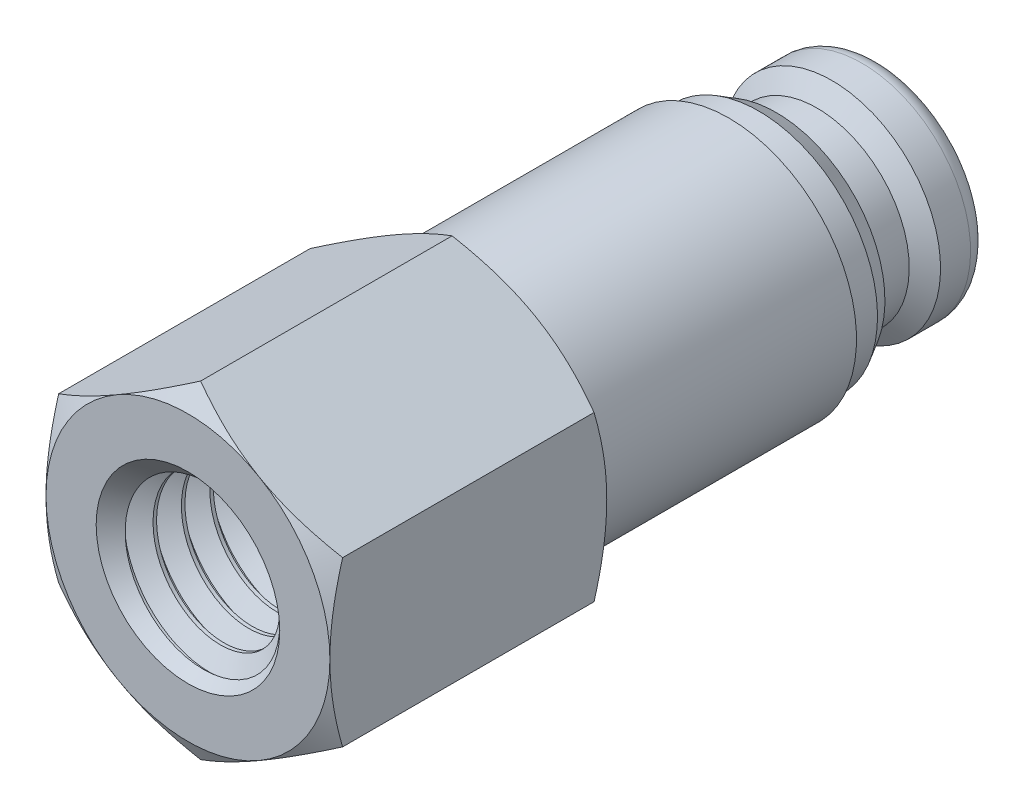
SolidWorks part; units mm, degrees
ref_plane "Front Plane" through (0, 0, 0) normal (0, 0, 1) x (1, 0, 0)
ref_plane "Top Plane" through (0, 0, 0) normal (0, 1, 0) x (1, 0, 0)
ref_plane "Right Plane" through (0, 0, 0) normal (1, 0, 0) x (0, 0, -1)
sketch "Sketch1" plane through (0, 0, 0) normal (0, 0, 1) x (1, 0, 0)
  line L1 (0, 4.6188) -> (-4, 2.3094)
  line L2 (-4, 2.3094) -> (-4, -2.3094)
  line L3 (-4, -2.3094) -> (0, -4.6188)
  line L4 (0, -4.6188) -> (4, -2.3094)
  line L5 (4, -2.3094) -> (4, 2.3094)
  line L6 (4, 2.3094) -> (0, 4.6188)
  circle A0 centre (0, 0) radius 4 construction
  dimension "hex size" = 8
extrude "Extrude1" add sketch "Sketch1" against normal blind 7.8
sketch "Sketch2" plane through (0, 0, 0) normal (0, 0, 1) x (1, 0, 0)
  circle A0 centre (0, 0) radius 2.5
  dimension "pipe dia" = 5
extrude "Cut-Extrude1" cut sketch "Sketch2" against normal blind 6.5
sketch "Sketch3" plane through (0, 0, 0) normal (0, 0, 1) x (1, 0, 0)
  circle A1 centre (0, 0) radius 2.5
  circle A2 centre (0, 0) radius 2.5 construction
  point P4 (0, 2.5)
curve "Helix/Spiral1" pitch 0.8 height 7.3 turns 9.125 parameters "pitch"=0.8
sketch "Sketch4" plane through (0, 0, 0) normal (1, 0, 0) x (0, 0, -1)
  line L0 (-0.3, 1.9804) -> (0, 2.5) construction
  line L1 (-0.4, 1.9804) -> (-0.3, 1.9804)
  line L2 (-0.4, 1.9804) -> (-0.725, 2.5433)
  line L3 (-0.7, 2.5) -> (0, 2.5) construction
  line L4 (-0.75, 2.5866) -> (-0.35, 1.8938) construction
  line L5 (-0.55, 2.2402) -> (-0.15, 2.2402) construction
  line L7 (0.025, 2.5433) -> (-0.3, 1.9804)
  line L9 (-0.35, 1.8938) -> (0.05, 2.5866) construction
  line L10 (0.05, 2.5866) -> (-0.75, 2.5866) construction
  line L11 (-0.35, 2.5) -> (-0.35, 2.5866) construction
  line L12 (-0.725, 2.5433) -> (0.025, 2.5433)
  point P16 (-0.35, 2.5433)
  dimension "D1" = 60
  dimension "D2" = 0.0866
  dimension "D3" = 0.4
  dimension "D4" = 0.6928
sweep "Sweep1" add profiles "Sketch4" path "Helix/Spiral1"
sketch "Sketch5" plane through (0, 0, 0) normal (0, 0, 1) x (1, 0, 0)
  line L0 (0, 0) -> (-1.2933, -2.2401) construction
  line L1 (-1.2933, -2.2401) -> (-2, -3.4641) construction
  line L2 (-4, -2.3094) -> (0, -4.6188) construction
  circle A0 centre (0, 0) radius 2.5866
extrude "Cut-Extrude2" cut sketch "Sketch5" against normal through all draft 45 and the other way through all draft 45
sketch "Sketch6" plane through (0, 0, 0) normal (0, 0, 1) x (1, 0, 0)
  circle A0 centre (0, 0) radius 4 construction
  circle A1 centre (0, 0) radius 4
extrude "Cut-Extrude3" cut sketch "Sketch6" against normal through all draft 60 flip side to cut
sketch "Sketch7" plane through (0, 0, 0) normal (1, 0, 0) x (0, 0, -1)
  line L0 (0, 0) -> (7.8, 0) construction
  line L1 (7.8, 3.6) -> (15.237, 3.6)
  line L2 (7.8, 3.6) -> (7.8, 2)
  line L3 (7.8, 2) -> (19.119, 2)
  line L4 (19.5, 2.552) -> (19.5, 2.381)
  line L7 (18.1453, 3.06) -> (18.992, 3.06)
  line L8 (19.119, 2) -> (19.5, 2.381)
  line L9 (16.579, 3.06) -> (16.579, 2.601)
  line L10 (16.579, 2.601) -> (17.722, 2.601)
  line L11 (17.722, 2.3268) -> (17.722, 2.601)
  line L12 (7.8, -2.3094) -> (7.8, 2.3094) construction
  line L13 (17.722, 2.3268) -> (18.1453, 3.06)
  line L14 (15.237, 3.6) -> (15.237, 3.346)
  line L15 (15.237, 3.346) -> (16.0836, 3.346)
  line L16 (16.0836, 3.346) -> (16.579, 3.06)
  arc A0 (18.992, 3.06) -> (19.5, 2.552) centre (18.992, 2.552) cw
  point P1 (19.5, 2)
  dimension "D4" = 0.508
  dimension "D1" = 5.202
  dimension "Tube OD" = 4
  dimension "G" = 7.2
  dimension "H" = 19.5
  dimension "D2" = 1.778
  dimension "D3" = 1.143
  dimension "D5" = 60
  dimension "D6" = 6.12
  dimension "D8" = 30
  dimension "D9" = 0.254
revolve "Revolve1" add sketch "Sketch7" angle 360 about L0
sketch "Sketch8" plane through (0, 0, -19.5) normal (0, 0, -1) x (-1, 0, 0)
  circle A3 centre (0, 0) radius 1.492
  circle A4 centre (0, 0) radius 1.492
  dimension "D1" = 0.508
extrude "Cut-Extrude4" cut sketch "Sketch8" against normal up to surface (13 mm away)
sketch "Sketch9" plane through (0, 0, -7.8) normal (0, 0, -1) x (-1, 0, 0)
  circle A0 centre (0, 0) radius 4 construction
  circle A1 centre (0, 0) radius 4
extrude "Cut-Extrude5" cut sketch "Sketch9" against normal through all draft 60 and the other way through all draft 60 flip side to cut
equation "\"D2@Sketch4\" = \"D4@Sketch4\" * 1/8"
equation "\"D3@Sketch4\" = \"pitch@Helix/Spiral1\"*.5"
equation "\"D3@Helix/Spiral1\" = \"thread length@Cut-Extrude1\"+\"pitch@Helix/Spiral1\""
equation "\"G@Sketch7\" = \"hex size@Sketch1\"*.9"
equation "\"D6@Sketch7\" = \"G@Sketch7\"*.85"
equation "\"D1@Sketch7\" = \"D6@Sketch7\"*.85"
equation "\"E@Extrude1\" = \"thread length@Cut-Extrude1\"*1.2"
